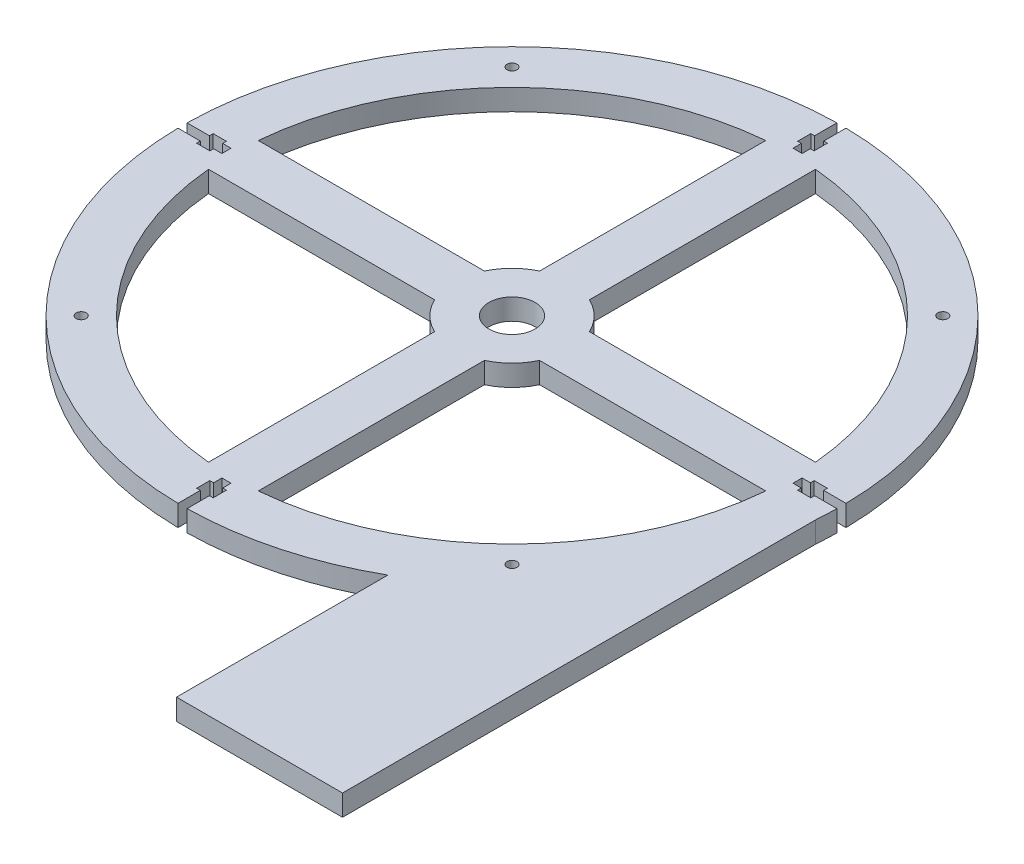
SolidWorks part; units mm, degrees
note: '?' marks a value the reader was unsure of.
material "6061 Alloy"
ref_plane "Front Plane" through (0, 0, 0) normal (0, 0, 1) x (1, 0, 0)
ref_plane "Top Plane" through (0, 0, 0) normal (0, 1, 0) x (1, 0, 0)
ref_plane "Right Plane" through (0, 0, 0) normal (1, 0, 0) x (0, 0, -1)
sketch "Sketch1" plane through (0, 0, 0) normal (0, 1, 0) x (1, 0, 0)
  line L0 (0, -99.238) -> (0, 99.238) construction
  line L1 (-99.238, 0) -> (99.238, 0) construction
  line L2 (-83.9035, -7.5) -> (-15.8114, -7.5)
  line L3 (7.5, -83.9035) -> (7.5, -15.8114)
  line L4 (-83.9035, 7.5) -> (-15.8114, 7.5)
  line L5 (-7.5, -83.9035) -> (-7.5, -15.8114)
  line L6 (-7.5, -99.238) -> (-7.5, 99.238) construction
  line L7 (7.5, -99.238) -> (7.5, 99.238) construction
  line L8 (-99.238, -7.5) -> (99.238, -7.5) construction
  line L9 (-99.238, 7.5) -> (99.238, 7.5) construction
  line L11 (98.9542, -7.5) -> (98.9542, -150)
  line L16 (98.9542, -150) -> (48.9542, -150)
  line L17 (48.9542, -150) -> (48.9542, -86.323)
  line L18 (7.5, -98.9542) -> (7.5, -83.9035) construction
  line L19 (-7.5, -98.9542) -> (-7.5, -83.9035) construction
  line L20 (-98.9542, -7.5) -> (-83.9035, -7.5) construction
  line L21 (-98.9542, 7.5) -> (-83.9035, 7.5) construction
  line L22 (-7.5, 83.9035) -> (-7.5, 98.9542) construction
  line L23 (7.5, 83.9035) -> (7.5, 98.9542) construction
  line L24 (83.9035, 7.5) -> (98.9542, 7.5) construction
  line L25 (83.9035, -7.5) -> (98.9542, -7.5) construction
  line L26 (-7.5, -7.5) -> (0, -7.5) construction
  line L27 (15.8114, -7.5) -> (83.9035, -7.5)
  line L28 (0, -7.5) -> (7.5, -7.5) construction
  line L29 (7.5, -7.5) -> (7.5, 0) construction
  line L30 (7.5, 15.8114) -> (7.5, 83.9035)
  line L31 (0, 7.5) -> (7.5, 7.5) construction
  line L32 (15.8114, 7.5) -> (83.9035, 7.5)
  line L33 (7.5, 0) -> (7.5, 7.5) construction
  line L34 (-7.5, 7.5) -> (0, 7.5) construction
  line L35 (-7.5, 0) -> (-7.5, 7.5) construction
  line L36 (-7.5, 15.8114) -> (-7.5, 83.9035)
  line L37 (-7.5, -7.5) -> (-7.5, 0) construction
  line L38 (7.5, -15.8114) -> (7.5, -7.5) construction
  line L39 (7.5, -7.5) -> (15.8114, -7.5) construction
  line L40 (-7.5, -15.8114) -> (-7.5, -7.5) construction
  line L41 (-15.8114, -7.5) -> (-7.5, -7.5) construction
  line L42 (-15.8114, 7.5) -> (-7.5, 7.5) construction
  line L43 (-7.5, 7.5) -> (-7.5, 15.8114) construction
  line L44 (7.5, 7.5) -> (7.5, 15.8114) construction
  line L45 (7.5, 7.5) -> (15.8114, 7.5) construction
  arc A0 (98.9542, -14.4246) -> (48.9542, -87.198) centre (0, 0) ccw construction
  arc A1 (98.9542, -7.5) -> (48.9542, -86.323) centre (0, 0) ccw
  arc A2 (7.5, -83.9035) -> (83.9035, -7.5) centre (0, 0) ccw
  arc A3 (48.9542, -87.198) -> (98.9542, -14.4246) centre (0, 0) ccw construction
  arc A4 (48.9542, -86.323) -> (98.9542, -7.5) centre (0, 0) ccw construction
  arc A5 (-7.5, -83.9035) -> (0, -84.238) centre (0, 0) ccw construction
  arc A6 (0, -84.238) -> (7.5, -83.9035) centre (0, 0) ccw construction
  arc A7 (-84.238, 0) -> (-83.9035, -7.5) centre (0, 0) ccw construction
  arc A8 (-83.9035, -7.5) -> (-7.5, -83.9035) centre (0, 0) ccw
  arc A9 (-83.9035, 7.5) -> (-84.238, 0) centre (0, 0) ccw construction
  arc A10 (0, 84.238) -> (-7.5, 83.9035) centre (0, 0) ccw construction
  arc A11 (-7.5, 83.9035) -> (-83.9035, 7.5) centre (0, 0) ccw
  arc A12 (7.5, 83.9035) -> (0, 84.238) centre (0, 0) ccw construction
  arc A13 (84.238, 0) -> (83.9035, 7.5) centre (0, 0) ccw construction
  arc A14 (83.9035, 7.5) -> (7.5, 83.9035) centre (0, 0) ccw
  arc A15 (83.9035, -7.5) -> (84.238, 0) centre (0, 0) ccw construction
  arc A16 (7.5, -15.8114) -> (15.8114, -7.5) centre (0, 0) ccw
  arc A17 (-7.5, -15.8114) -> (0, -17.5) centre (0, 0) ccw construction
  arc A18 (0, -17.5) -> (7.5, -15.8114) centre (0, 0) ccw construction
  arc A19 (-17.5, 0) -> (-15.8114, -7.5) centre (0, 0) ccw construction
  arc A20 (-15.8114, -7.5) -> (-7.5, -15.8114) centre (0, 0) ccw
  arc A21 (-15.8114, 7.5) -> (-17.5, 0) centre (0, 0) ccw construction
  arc A22 (0, 17.5) -> (-7.5, 15.8114) centre (0, 0) ccw construction
  arc A23 (-7.5, 15.8114) -> (-15.8114, 7.5) centre (0, 0) ccw
  arc A24 (7.5, 15.8114) -> (0, 17.5) centre (0, 0) ccw construction
  arc A25 (17.5, 0) -> (15.8114, 7.5) centre (0, 0) ccw construction
  arc A26 (15.8114, 7.5) -> (7.5, 15.8114) centre (0, 0) ccw
  arc A27 (15.8114, -7.5) -> (17.5, 0) centre (0, 0) ccw construction
  point P7 (0, 0)
  point P11 (0, 0)
  dimension "D1" = 200
  dimension "D2" = 0.762
  dimension "D3" = 15
  dimension "D6" = 150
  dimension "D7" = 50
  dimension "D8" = 35
  dimension "D4" = 7.5
  dimension "D5" = 7.5
extrude "Boss-Extrude1" add sketch "Sketch1" along normal mid plane 6.35
sketch "Sketch2" plane through (0, 0, 0) normal (0, 1, 0) x (1, 0, 0)
  line L0 (-1.375, 86) -> (-1.375, 100)
  line L1 (-1.375, 86) -> (1.375, 86)
  line L2 (-1.375, 100) -> (1.375, 100)
  line L3 (1.375, 86) -> (1.375, 100)
  line L4 (-1.375, 86) -> (1.375, 100) construction
  line L5 (-1.375, 100) -> (1.375, 86) construction
  line L6 (-2.5, 88.5) -> (-2.5, 92.5)
  line L7 (-2.5, 88.5) -> (2.5, 88.5)
  line L8 (-2.5, 92.5) -> (2.5, 92.5)
  line L9 (2.5, 88.5) -> (2.5, 92.5)
  line L10 (-2.5, 88.5) -> (2.5, 92.5) construction
  line L11 (-2.5, 92.5) -> (2.5, 88.5) construction
  line L12 (0, -1000) -> (0, 49000) construction
  line L13 (-1000, 0) -> (49000, 0) construction
  point P1 (0, 93)
  point P2 (0, 90.5)
  dimension "D1" = 2.75
  dimension "D2" = 14
  dimension "D3" = 4
  dimension "D4" = 5
  dimension "D5" = 2.5
  dimension "D6" = 100
extrude "Cut-Extrude1" cut sketch "Sketch2" against normal through all both and the other way through all contours L7 L0 L1 L3 | L8 L0 L7 L3 | L7 L9 L8 L3 | L0 L8 L3 L2 | L8 L6 L7 L0
ref_axis "Axis1" through (0, 0, 0) along (0, 1, 0)?
pattern_circular "CirPattern1" count 4 over 360 about axis through (0, 0, 0) along (0, 1, 0) of "Cut-Extrude1"
hole_wizard "Ø3.0 (3) Diameter Hole1" positions "Sketch3" profile "Sketch4" hole size "Ø3.0" standard "ANSI Metric" end condition up to next
sketch "Sketch3" plane through (0, 3.175, 0) normal (0, 1, 0) x (1, 0, 0)
  line L11 (707.1068, -707.1068) -> (0, 0) construction
  line L13 (-698.3159, -698.3159) -> (34217.48, 34217.48) construction
  line L14 (0, 0) -> (-34648.2323, 34648.2323) construction
  line L15 (-70.1719, 70.1719) -> (-59.5653, 59.5653)
  line L17 (59.5653, 59.5653) -> (70.1719, 70.1719)
  line L19 (70.1719, -70.1719) -> (59.5653, -59.5653)
  line L24 (-59.5653, -59.5653) -> (-70.1719, -70.1719)
  arc A8 (-1.375, 99.2285) -> (-99.2285, 1.375) centre (0, 0) ccw construction
  arc A9 (-7.5, 83.9035) -> (-83.9035, 7.5) centre (0, 0) ccw construction
  arc A10 (7.5, -83.9035) -> (83.9035, -7.5) centre (0, 0) ccw construction
  arc A12 (99.2285, 1.375) -> (1.375, 99.2285) centre (0, 0) ccw construction
  arc A13 (83.9035, 7.5) -> (7.5, 83.9035) centre (0, 0) ccw construction
  arc A14 (-83.9035, -7.5) -> (-7.5, -83.9035) centre (0, 0) ccw construction
  arc A15 (-99.2285, -1.375) -> (-1.375, -99.2285) centre (0, 0) ccw construction
  point P454 (-64.8686, 64.8686)
  point P456 (64.8686, 64.8686)
  point P458 (64.8686, -64.8686)
  point P460 (-64.8686, -64.8686)
sketch "Sketch4" plane through (-64.8686, 3.175, 64.8686) normal (1, 0, 0) x (0, 0, 1)
  line L0 (0, 0) -> (0, 6.35)
  line L1 (0, 6.35) -> (1.5, 6.35)
  line L2 (1.5, 6.35) -> (1.5, 0)
  line L5 (1.5, 0) -> (0, 0)
  line L11 (0, -6.35) -> (0, 107.95) construction
  dimension "Thru Hole Dia." = 3
  dimension "Thru Hole Depth" = 6.35
hole_wizard "1/2 Clearance Hole1" positions "Sketch5" profile "Sketch6" hole size "1/2" standard "ANSI Inch" end condition up to next
sketch "Sketch5" plane through (0, 3.175, 0) normal (0, 1, 0) x (1, 0, 0)
  point P0 (0, 0)
sketch "Sketch6" plane through (0, 3.175, 0) normal (1, 0, 0) x (0, 0, 1)
  line L0 (0, 0) -> (0, 6.35)
  line L1 (0, 6.35) -> (6.9456, 6.35)
  line L2 (6.9456, 6.35) -> (6.9456, 0)
  line L5 (6.9456, 0) -> (0, 0)
  line L11 (0, -6.35) -> (0, 107.95) construction
  dimension "Thru Hole Dia." = 13.8913
  dimension "Thru Hole Depth" = 6.35
hole_wizard "M4 Clearance Slot1" [suppressed] positions "Sketch11" profile "Sketch12" size "M4" standard "ANSI Metric"
sketch "Sketch11" plane through (0, 3.175, 0) normal (0, 1, 0) x (1, 0, 0)
  line L1 (10.88, -3.94) -> (20.88, -3.94) construction
  point P0 (15.88, -3.94)
  point P2 (15.88, 3.94)
  dimension "D1" = 3.94
  dimension "D2" = 15.88
  dimension "D3" = 3.94
  dimension "D4" = 10
sketch "Sketch12" plane through (15.88, 3.175, 3.94) normal (1, 0, 0) x (0, 0, 1)
  line L0 (0, 0) -> (0, 6.35)
  line L1 (0, 6.35) -> (2.15, 6.35)
  line L2 (2.15, 6.35) -> (2.15, 0)
  line L5 (2.15, 0) -> (0, 0)
  line L11 (0, -6.35) -> (0, 107.95) construction
  dimension "Thru Hole Dia." = 4.3
  dimension "Thru Hole Depth" = 6.35
fillet "Fillet1" [suppressed] radius 3.175
